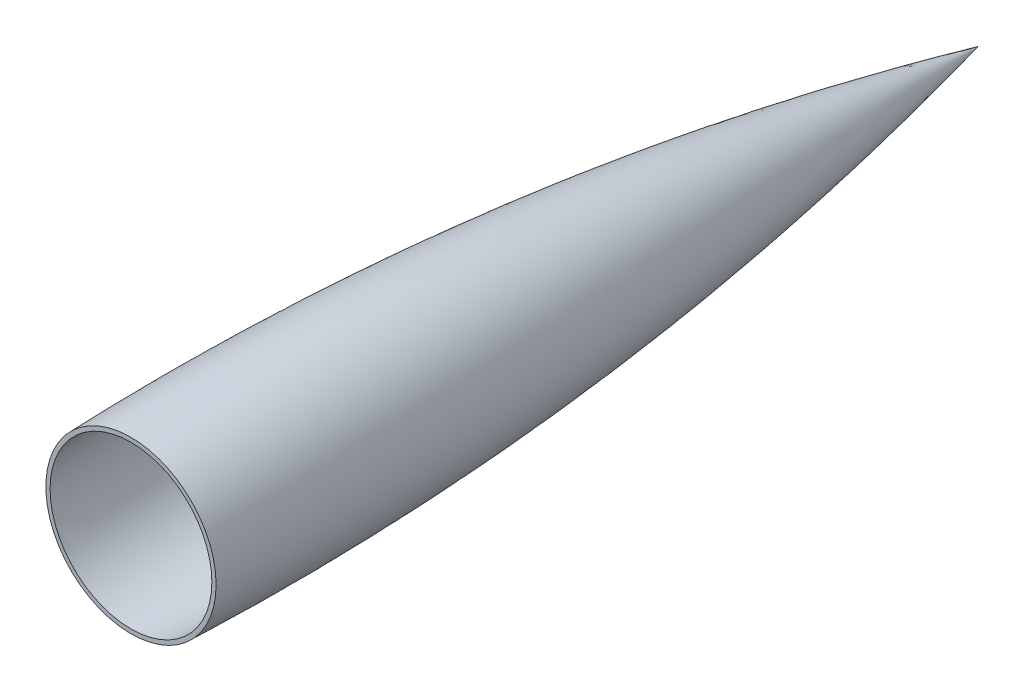
SolidWorks part; units mm, degrees
ref_plane "Front Plane" through (0, 0, 0) normal (0, 0, 1) x (1, 0, 0)
ref_plane "Top Plane" through (0, 0, 0) normal (0, 1, 0) x (1, 0, 0)
ref_plane "Right Plane" through (0, 0, 0) normal (1, 0, 0) x (0, 0, -1)
sketch "Sketch1" plane through (0, 0, 0) normal (0, 1, 0) x (1, 0, 0)
  line L0 (0, 0) -> (51.054, 0)
  line L1 (51.054, 0) -> (51.054, 508)
  arc A0 (0, 0) -> (51.054, 508) centre (1975.6255, 58.0151) cw
  dimension "D1" = 508
  dimension "D2" = 51.054
revolve "Revolve1" add sketch "Sketch1" angle 360 about L1
shell "Shell1" thickness 2.54 removed face at (102.108, 0, 0)
